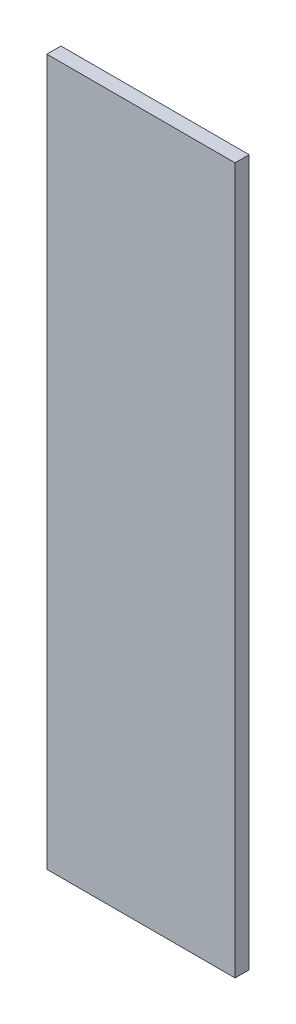
SolidWorks part; units mm, degrees
note: The reader was unsure of these and kept them because the rebuilt part matched: thickness of "Base-Flange1", "Sheet-Metal1".
material "Plain Carbon Steel"
ref_plane "Front Plane" through (0, 0, 0) normal (0, 0, 1) x (1, 0, 0)
ref_plane "Top Plane" through (0, 0, 0) normal (0, 1, 0) x (1, 0, 0)
ref_plane "Right Plane" through (0, 0, 0) normal (1, 0, 0) x (0, 0, -1)
sketch "Sketch1" plane through (0, 0, 0) normal (0, 0, 1) x (1, 0, 0)
  line L1 (0, 0) -> (40, 0)
  line L2 (0, 0) -> (0, 150)
  line L3 (0, 150) -> (40, 150)
  line L4 (40, 0) -> (40, 150)
  dimension "D1" = 40
  dimension "D2" = 150
base flange "Base-Flange1" sketch "Sketch1" thickness 3 reverse thickness direction no parameters "D1"=2.54
sketch "Bend-Lines1" [suppressed] plane through (0, 0, 0) normal (0, 1, 0) x (1, 0, 0)
sketch "Bounding-Box1" [suppressed] plane through (0, 0, 0) normal (0, 1, 0) x (1, 0, 0)
sheet metal parameters "Sheet-Metal1" thickness 3 parameters "D1"=2.54
flat pattern "Flat-Pattern1" [suppressed]
sketch "Bend-Lines2" plane through (0, 0, 0) normal (0, 1, 0) x (1, 0, 0)
sketch3d "Bounding-Box2" [suppressed]
  line L0 (40, 150, 0) -> (40, 0, 0) construction
  line L1 (0, 150, 0) -> (0, 0, 0) construction
  line L2 (40, 150, 0) -> (0, 150, 0) construction
  line L3 (40, 0, 0) -> (0, 0, 0) construction
